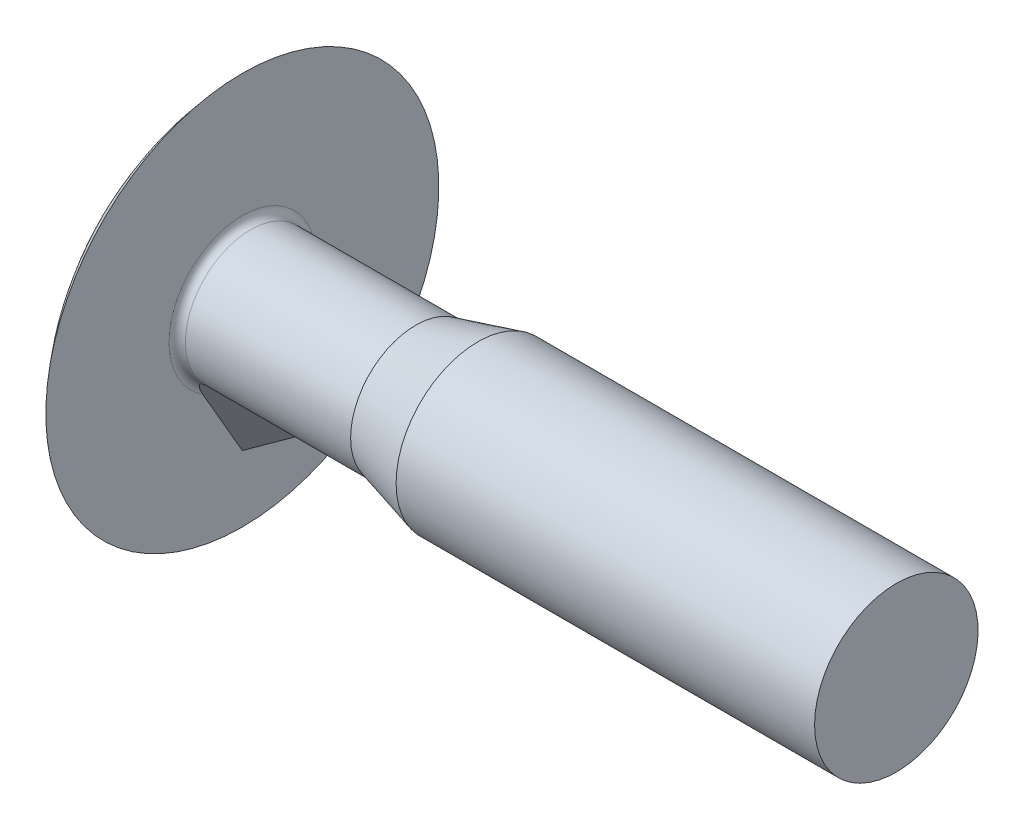
SolidWorks part; units mm, degrees
ref_plane "Front" through (0, 0, 0) normal (0, 0, 1) x (1, 0, 0)
ref_plane "Top" through (0, 0, 0) normal (0, 1, 0) x (1, 0, 0)
ref_plane "Right" through (0, 0, 0) normal (1, 0, 0) x (0, 0, -1)
sketch "Sketch1" plane through (-7.6906, 4.3277, 0) normal (0, 0, 1) x (0, 1, 0)
  line L0 (-4.3277, -12.2906) -> (-16.3461, -12.2906)
  line L1 (-4.3277, 1.3165) -> (-4.3277, -29.2605) construction
  line L2 (-4.3277, -12.2906) -> (-4.3277, -7.6906)
  arc A0 (-4.3277, -7.6906) -> (-16.3461, -12.2906) centre (-4.3277, -25.6906) ccw
  dimension "r" = 18
  dimension "k" = 4.6
revolve "BaseHead" add sketch "Sketch1" angle 360 about L1
sketch "Sketch2" plane through (4.6, 0, 0) normal (1, 0, 0) x (0, 0, -1)
  circle A0 centre (0, 0) radius 5
extrude "BaseBody" add sketch "Sketch2" along normal blind 40
cosmetic thread "ThreadCosmetic1" [suppressed] parameters "b"=25.594, "D2"=8.376
sketch "Sketch3" plane through (-15.8544, 0, 20.8544) normal (0, 1, 0) x (0, 0, -1)
  line L0 (20.8544, 6.1636) -> (20.8544, -42.8724) construction
  line L1 (25.8544, -34.8604) -> (24.8362, -31.0604)
  line L2 (20.8544, -60.4544) -> (20.8544, -20.4544) construction
  line L3 (24.8362, -31.0604) -> (24.8362, -20.4544)
  line L4 (25.8544, -60.4544) -> (25.8544, -20.4544) construction
  line L5 (24.8362, -20.4544) -> (25.8544, -20.4544)
  line L6 (25.8544, -20.4544) -> (25.8544, -34.8604)
  line L7 (15.8544, -20.4544) -> (25.8544, -20.4544) construction
  line L8 (8.8361, -20.4544) -> (32.8727, -20.4544) construction
  line L9 (15.8544, -60.4544) -> (25.8544, -60.4544) construction
  dimension "D1" = 15
  dimension "x" = 3.8
revolve "Cut-Revolve1" cut sketch "Sketch3" angle 360 about L0
fillet "Fillet1" radius 0.5 1 edges at (4.6, 0, 3.9818)
ref_plane "Plan1" through (10.1, 0, 0) normal (1, 0, 0) x (0, 0, -1)
sketch "Sketch4" plane through (4.6, 10.7187, 8.8426) normal (1, 0, 0) x (0, 0, 1)
  line L0 (-12.291, 12.7096) -> (-8.8426, 18.6823)
  line L1 (-8.8426, 18.6823) -> (-5.3943, 12.7096)
  line L2 (-12.291, 12.7096) -> (-5.3943, 12.7096)
  circle A0 centre (-8.8426, 10.7187) radius 3.9818 construction
  point P5 (-8.8426, 12.7096)
  dimension "D1" = 60
sketch "Sketch5" plane through (10.1, 0, 0) normal (1, 0, 0) x (0, 0, -1)
  line L0 (0, 0) -> (0, -9.3883) construction
  circle A0 centre (0, 0) radius 3.9818 construction
  circle A1 centre (0, 0) radius 3.9818 construction
  point P6 (0, -3.9818)
loft "Nib" add profiles "Sketch4", "Sketch5"
sketch "Sketch6" plane through (0, 0, 0) normal (0, 0, 1) x (1, 0, 0)
  line L0 (44.194, 5.2) -> (45.006, 5.2)
  line L1 (45.006, 5.2) -> (45.006, 5)
  line L2 (45.006, 5) -> (44.6, 4.2968)
  line L3 (44.194, 5) -> (44.6, 4.2968)
  line L4 (44.194, 5.2) -> (44.194, 5)
  line L5 (44.6, -5) -> (44.6, 5) construction
  line L6 (44.194, 5) -> (45.006, 5) construction
  line L7 (44.6, 5) -> (44.6, 4.2968) construction
  line L8 (44.6, 5) -> (19.006, 5) construction
  line L9 (0, 0) -> (56.0764, 0) construction
  point P5 (44.6, 5.2)
revolve "Cut-Revolve10" [suppressed] cut sketch "Sketch6" angle 360 about L9
pattern_linear "LPattern10" [suppressed] count 26 spacing 0.9744 along (-1, 0, 0) of bodies 105
equation "\"D2@Sketch6\" = (  \"d@Sketch2\" - \"D2@ThreadCosmetic1\" )  / 2"
equation "\"D3@LPattern10\" = 1.2 * \"D2@Sketch6\""
equation "\"D1@LPattern10\" = \"b@ThreadCosmetic1\" / \"D3@LPattern10\""
